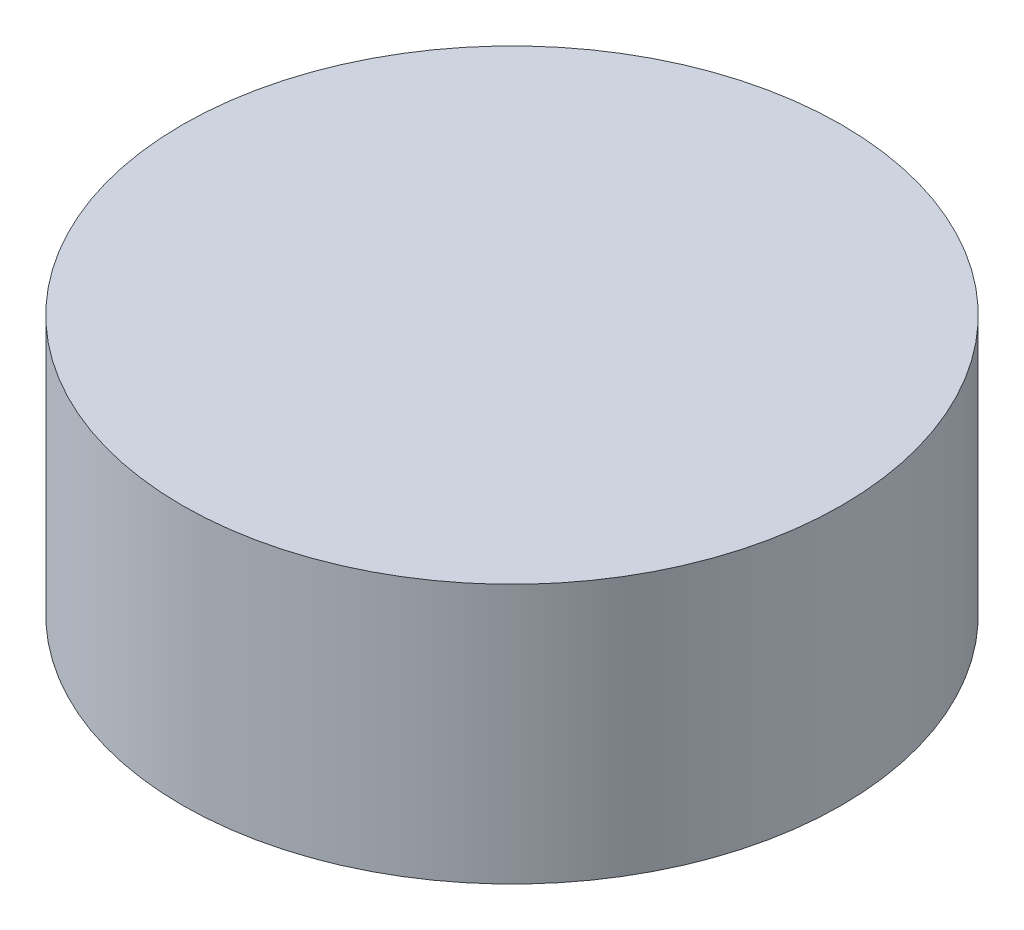
SolidWorks part; units mm, degrees
ref_plane "Front Plane" through (0, 0, 0) normal (0, 0, 1) x (1, 0, 0)
ref_plane "Top Plane" through (0, 0, 0) normal (0, 1, 0) x (1, 0, 0)
ref_plane "Right Plane" through (0, 0, 0) normal (1, 0, 0) x (0, 0, -1)
sketch "Sketch1" plane through (0, 0, 0) normal (0, 1, 0) x (1, 0, 0)
  circle A0 centre (0, 0) radius 76.2
  dimension "D1" = 152.4
extrude "Boss-Extrude1" add sketch "Sketch1" along normal blind 60
